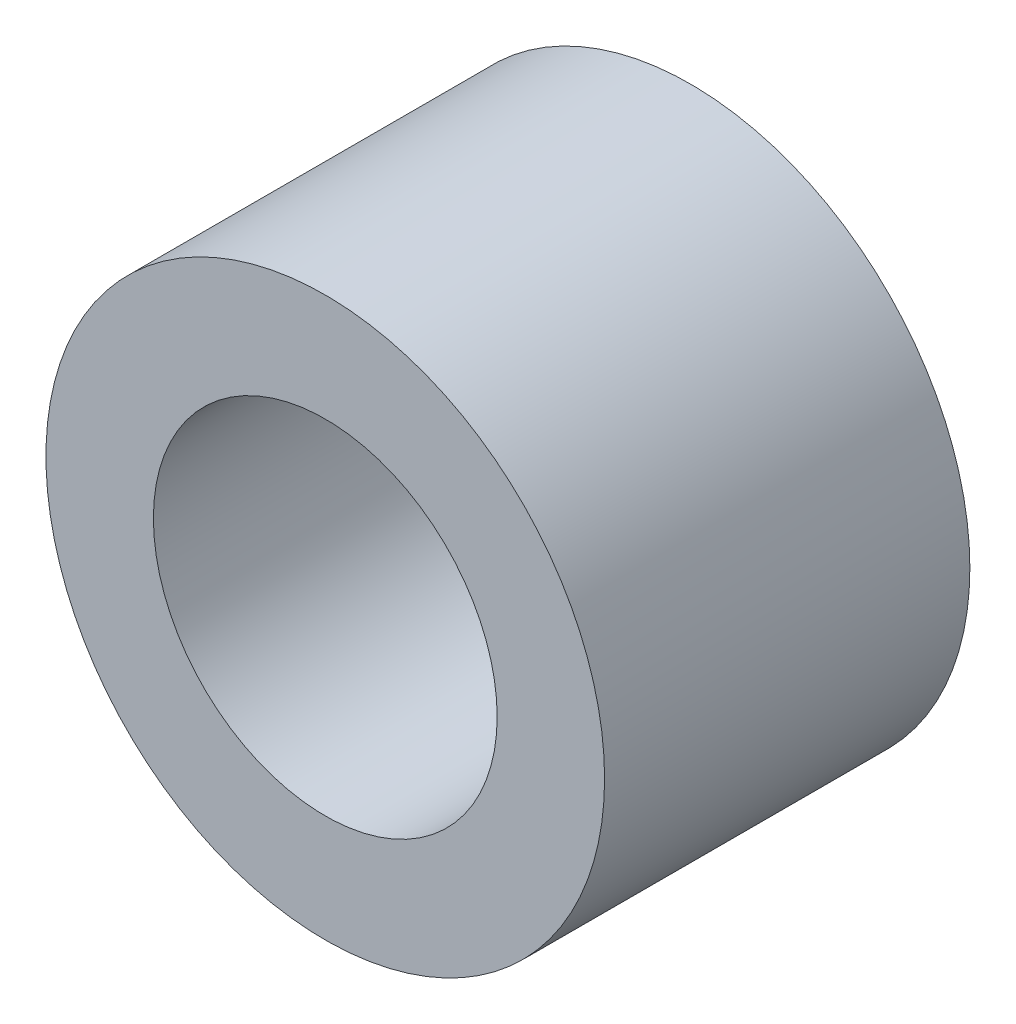
SolidWorks part; units mm, degrees
material "PETG"
ref_plane "Front Plane" through (0, 0, 0) normal (0, 0, 1) x (1, 0, 0)
ref_plane "Top Plane" through (0, 0, 0) normal (0, 1, 0) x (1, 0, 0)
ref_plane "Right Plane" through (0, 0, 0) normal (1, 0, 0) x (0, 0, -1)
sketch "Sketch1" plane through (0, 0, 0) normal (0, 0, 1) x (1, 0, 0)
  circle A0 centre (0, 0) radius 4
  circle A1 centre (0, 0) radius 6.5
  dimension "D1" = 8
  dimension "D2" = 13
extrude "Boss-Extrude1" add sketch "Sketch1" along normal mid plane 8.5
